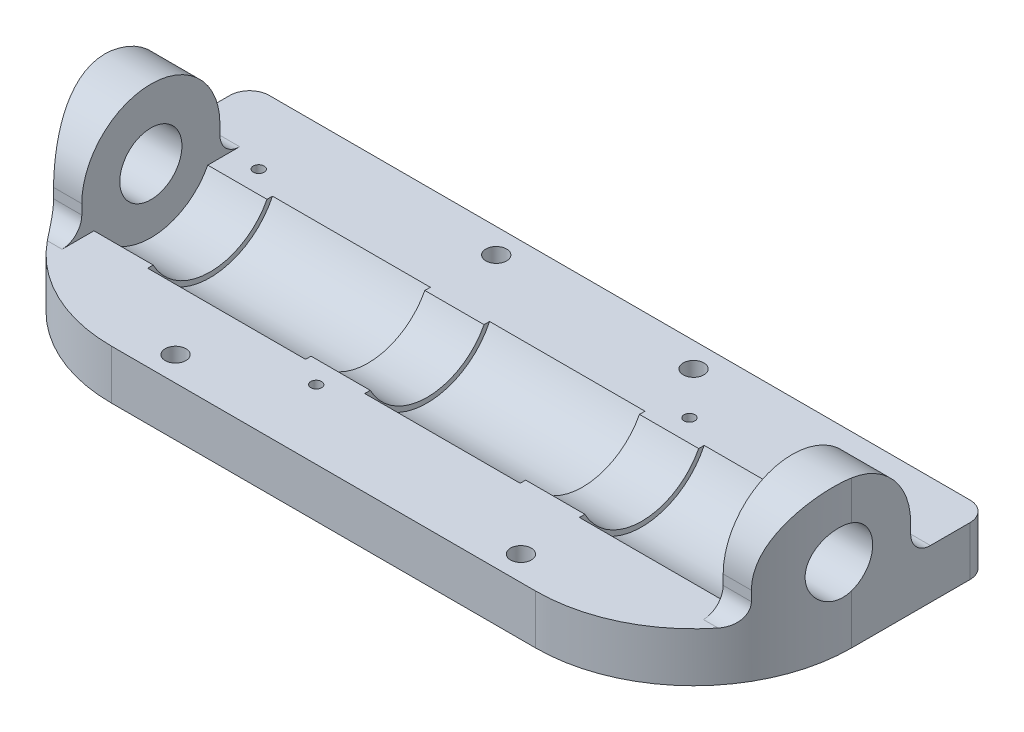
SolidWorks part; units mm, degrees
ref_plane "Front Plane" through (0, 0, 0) normal (0, 0, 1) x (1, 0, 0)
ref_plane "Top Plane" through (0, 0, 0) normal (0, 1, 0) x (1, 0, 0)
ref_plane "Right Plane" through (0, 0, 0) normal (1, 0, 0) x (0, 0, -1)
sketch "Sketch1" plane through (0, 0, 0) normal (1, 0, 0) x (0, 0, -1)
  line L0 (-12.6491, -6) -> (-30, -6)
  line L1 (-30, -6) -> (-30, -16)
  line L2 (-30, -16) -> (30, -16)
  line L3 (30, -16) -> (30, -6)
  line L4 (30, -6) -> (12.6491, -6)
  line L5 (0, 0) -> (0, -16) construction
  arc A0 (-12.6491, -6) -> (12.6491, -6) centre (0, 0) ccw
  dimension "D1" = 14
  dimension "D2" = 16
  dimension "D3" = 60
  dimension "D4" = 10
extrude "Boss-Extrude1" add sketch "Sketch1" along normal blind 75 and the other way blind 75
sketch "Sketch2" plane through (75, 0, 0) normal (1, 0, 0) x (0, 0, -1)
  line L0 (-30, -16) -> (30, -16) construction
  line L1 (-14, 0) -> (-14, -16)
  line L2 (-14, -16) -> (14, -16)
  line L3 (14, -16) -> (14, 0)
  circle A0 centre (0, 0) radius 6.3
  arc A1 (14, 0) -> (-14, 0) centre (0, 0) ccw
  arc A2 (-12.6491, -6) -> (12.6491, -6) centre (0, 0) ccw construction
  dimension "D1" = 12.6
extrude "Boss-Extrude2" add sketch "Sketch2" against normal blind 10
sketch "Sketch3" plane through (-75, 0, 0) normal (-1, 0, 0) x (0, 0, 1)
  line L0 (-14, 0) -> (-14, -16)
  line L1 (30, -16) -> (-30, -16) construction
  line L2 (-14, -16) -> (14, -16)
  line L3 (14, -16) -> (14, 0)
  circle A0 centre (0, 0) radius 6.3
  arc A1 (14, 0) -> (-14, 0) centre (0, 0) ccw
  circle A2 centre (0, 0) radius 6.3 construction
  arc A3 (14, 0) -> (-14, 0) centre (0, 0) ccw construction
extrude "Boss-Extrude3" add sketch "Sketch3" against normal blind 10
sketch "Sketch4" plane through (0, -6, 0) normal (0, 1, 0) x (1, 0, 0)
  circle A0 centre (-15.4853, -16) radius 1.1
  circle A1 centre (-59.1364, 16) radius 1.1
  circle A2 centre (28.1658, 16) radius 1.1
  dimension "D1" = 2.2
extrude "Cut-Extrude1" cut sketch "Sketch4" against normal through all
sketch "Sketch5" plane through (0, -16, 0) normal (0, -1, 0) x (1, 0, 0)
  line L0 (-35, 25) -> (35, 25) construction
  line L1 (-20, -25) -> (20, -25) construction
  line L19 (0, 25) -> (0, -25) construction
  line L20 (-75, 30) -> (75, 30) construction
  circle A0 centre (-35, 25) radius 2.1
  circle A1 centre (35, 25) radius 2.1
  circle A3 centre (-20, -25) radius 2.1
  circle A4 centre (20, -25) radius 2.1
  dimension "D1" = 4.2
  dimension "D2" = 5
  dimension "D3" = 70
  dimension "D4" = 40
extrude "Cut-Extrude2" cut sketch "Sketch5" against normal through all
sketch "Sketch7" plane through (0, -16, 0) normal (0, -1, 0) x (1, 0, 0)
  line L1 (-37.0785, 28.6) -> (-39.1569, 25)
  line L2 (-39.1569, 25) -> (-37.0785, 21.4)
  line L3 (-37.0785, 21.4) -> (-32.9215, 21.4)
  line L4 (-32.9215, 21.4) -> (-30.8431, 25)
  line L5 (-30.8431, 25) -> (-32.9215, 28.6)
  line L6 (-32.9215, 28.6) -> (-37.0785, 28.6)
  line L7 (32.9215, 28.6) -> (30.8431, 25)
  line L8 (30.8431, 25) -> (32.9215, 21.4)
  line L9 (32.9215, 21.4) -> (37.0785, 21.4)
  line L10 (37.0785, 21.4) -> (39.1569, 25)
  line L11 (39.1569, 25) -> (37.0785, 28.6)
  line L12 (37.0785, 28.6) -> (32.9215, 28.6)
  line L19 (-22.0785, -21.4) -> (-24.1569, -25)
  line L20 (-24.1569, -25) -> (-22.0785, -28.6)
  line L21 (-22.0785, -28.6) -> (-17.9215, -28.6)
  line L22 (-17.9215, -28.6) -> (-15.8431, -25)
  line L23 (-15.8431, -25) -> (-17.9215, -21.4)
  line L24 (-17.9215, -21.4) -> (-22.0785, -21.4)
  line L25 (17.9215, -21.4) -> (15.8431, -25)
  line L26 (15.8431, -25) -> (17.9215, -28.6)
  line L27 (17.9215, -28.6) -> (22.0785, -28.6)
  line L28 (22.0785, -28.6) -> (24.1569, -25)
  line L29 (24.1569, -25) -> (22.0785, -21.4)
  line L30 (22.0785, -21.4) -> (17.9215, -21.4)
  circle A0 centre (-35, 25) radius 3.6 construction
  circle A1 centre (35, 25) radius 3.6 construction
  circle A3 centre (-20, -25) radius 3.6 construction
  circle A4 centre (20, -25) radius 3.6 construction
  dimension "D1" = 7.2
extrude "Cut-Extrude3" cut sketch "Sketch7" against normal blind 6
fillet "Fillet1" radius 4 4 edges at (-70, -6, 14) (-70, -6, -14) (70, -6, -14) (70, -6, 14)
fillet "Fillet2" radius 4 2 edges at (-75, -11, -30) (75, -11, -30)
fillet "Fillet3" radius 32 2 edges at (75, -11, 30) (-75, -11, 30)
ref_plane "Plane1" through (-21, 0, 0) normal (-1, 0, 0) x (0, 0, 1)
ref_plane "Plane2" through (22.5, 0, 0) normal (1, 0, 0) x (0, 0, -1)
sketch "Sketch8" plane through (-21, 0, 0) normal (-1, 0, 0) x (0, 0, 1)
  line L0 (-10.9659, -6) -> (-13.7477, -6)
  line L1 (10.9659, -6) -> (13.7477, -6)
  line L2 (-26, -6) -> (-18, -6) construction
  arc A0 (-10.9659, -6) -> (10.9659, -6) centre (0, 0) ccw
  arc A1 (-13.7477, -6) -> (13.7477, -6) centre (0, 0) ccw
  dimension "D1" = 25
  dimension "D2" = 30
extrude "Boss-Extrude4" add sketch "Sketch8" against normal blind 12
extrude "Boss-Extrude5" add sketch "Sketch8<2>" against normal blind 12 from surface starting at plane "Plane2"
sketch "Sketch8<2>" plane through (-21, 0, 0) normal (-1, 0, 0) x (0, 0, 1) same geometry as "Sketch8"
ref_plane "Plane3" through (-65, 0, 0) normal (-1, 0, 0) x (0, 0, 1)
extrude "Boss-Extrude7" add sketch "Sketch8<4>" against normal blind 12 from surface starting at plane "Plane3"
sketch "Sketch8<4>" plane through (-21, 0, 0) normal (-1, 0, 0) x (0, 0, 1) same geometry as "Sketch8"
sketch "Sketch16" plane through (-65, 0, 0) normal (1, 0, 0) x (0, 0, -1)
  circle A0 centre (0, 0) radius 13
extrude "Cut-Extrude8" cut sketch "Sketch16" along normal up to surface (130 mm away) up to face at (65, -2.9571, 0)
